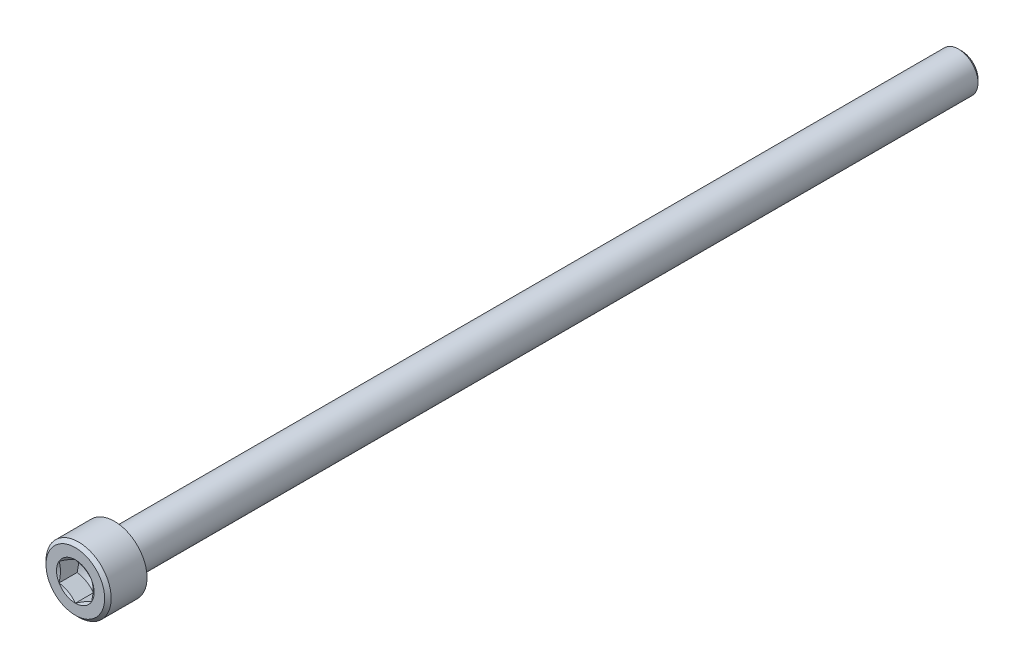
SolidWorks part; units mm, degrees
ref_plane "Front" through (0, 0, 0) normal (0, 0, 1) x (1, 0, 0)
ref_plane "Top" through (0, 0, 0) normal (0, 1, 0) x (1, 0, 0)
ref_plane "Right" through (0, 0, 0) normal (1, 0, 0) x (0, 0, -1)
sketch "Sketch1" plane through (0, 0, 0) normal (1, 0, 0) x (0, 0, -1)
  line L0 (0, 5) -> (-6, 5)
  line L1 (-6, 5) -> (-6, 0)
  line L2 (-6, 0) -> (130, 0)
  line L3 (130, 0) -> (130, 3)
  line L4 (130, 3) -> (0, 3)
  line L5 (0, 3) -> (0, 5)
  line L6 (0, 0) -> (12.7561, 0) construction
  dimension "l" = 130
  dimension "d" = 6
  dimension "k" = 6
  dimension "dk" = 10
revolve "Revolve1" add sketch "Sketch1" angle 360 about L2
sketch "Sketch7" plane through (0, 0, 0) normal (1, 0, 0) x (0, 0, -1)
  line L0 (-6.6396, 0) -> (3.6195, 0) construction
  line L1 (-6, 0) -> (-6, 2.5)
  line L2 (-6, 5) -> (-6, -5) construction
  line L3 (-6, 2.5) -> (-3, 2.5)
  line L4 (-3, 2.5) -> (-1.5566, 0)
  line L6 (-6, 0) -> (-1.5566, 0)
  dimension "D1" = 60
  dimension "S" = 5
  dimension "t" = 3
revolve "Cut-Revolve2" cut sketch "Sketch7" angle 360 about L6
chamfer "Chamfer1" distance 0.5 2 edges at (0, -3, -130) (0, -5, 6)
sketch "Sketch8" plane through (0, 0, 6) normal (0, 0, 1) x (1, 0, 0)
  line L1 (0, 2.8868) -> (-2.5, 1.4434)
  line L2 (-2.5, 1.4434) -> (-2.5, -1.4434)
  line L3 (-2.5, -1.4434) -> (0, -2.8868)
  line L4 (0, -2.8868) -> (2.5, -1.4434)
  line L5 (2.5, -1.4434) -> (2.5, 1.4434)
  line L6 (2.5, 1.4434) -> (0, 2.8868)
  circle A0 centre (0, 0) radius 2.5 construction
  circle A1 centre (0, 0) radius 2.5 construction
extrude "Cut-Extrude1" cut sketch "Sketch8" against normal up to surface (2.7767 mm away) up to face at (2.5, 0, 3)
sketch "Sketch9" plane through (0, 0, 0) normal (1, 0, 0) x (0, 0, -1)
  line L0 (-6, 2.5) -> (4.2695, 2.5) construction
  line L3 (-6.5, 3.7528) -> (-6.5, 2.5)
  line L4 (-6.5, 2.5) -> (-5.7767, 2.5)
  line L5 (-5.7767, 2.5) -> (-6.5, 3.7528)
  line L6 (-6, 5) -> (-6, -5) construction
  dimension "D1" = 60
  dimension "D2" = 0.5
revolve "Cut-Revolve3" cut sketch "Sketch9" angle 360 about axis through (0, 0, 6) along (0, 0, -1)
fillet "Fillet2" radius 0.25 1 edges at (0, -3, 0)
